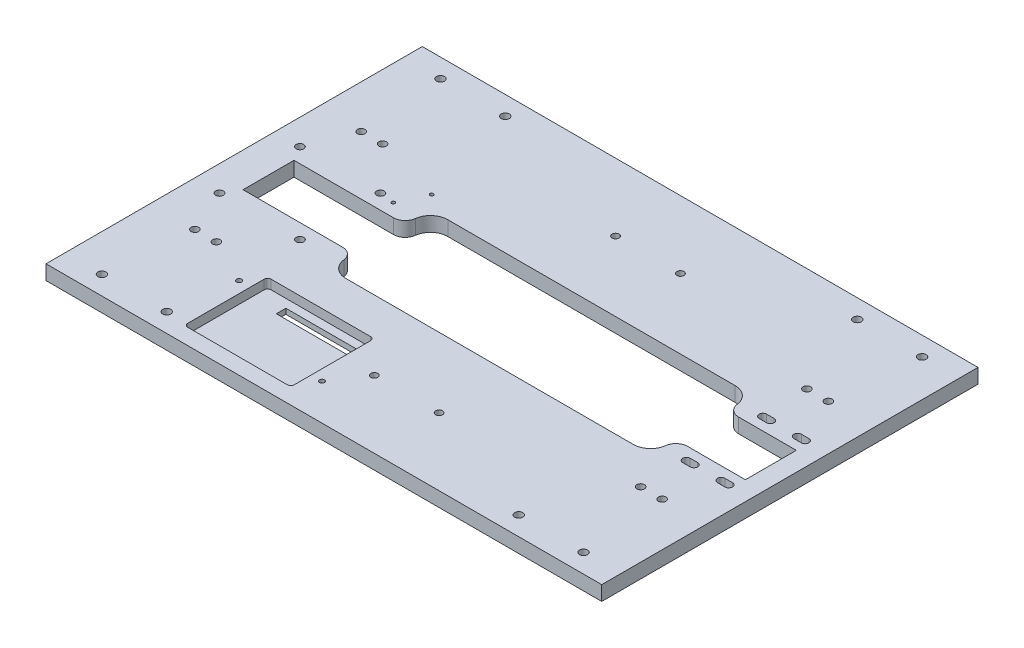
SolidWorks part; units mm, degrees
ref_plane "Front Plane" through (0, 0, 0) normal (0, 0, 1) x (1, 0, 0)
ref_plane "Top Plane" through (0, 0, 0) normal (0, 1, 0) x (1, 0, 0)
ref_plane "Right Plane" through (0, 0, 0) normal (1, 0, 0) x (0, 0, -1)
sketch "Sketch1" plane through (0, 0, 0) normal (0, 1, 0) x (1, 0, 0)
  line L1 (-240, 162.5) -> (240, 162.5)
  line L2 (-240, 162.5) -> (-240, -162.5)
  line L3 (-240, -162.5) -> (240, -162.5)
  line L4 (240, 162.5) -> (240, -162.5)
  line L5 (-240, 162.5) -> (240, -162.5) construction
  line L6 (-240, -162.5) -> (240, 162.5) construction
  point P0 (0, 0)
  dimension "D1" = 480
  dimension "D2" = 325
extrude "Boss-Extrude1" add sketch "Sketch1" along normal blind 12.6
sketch "Sketch2" plane through (0, 0, 0) normal (0, -1, 0) x (1, 0, 0)
  circle A0 centre (41.2474, -104.2) radius 3
  circle A1 centre (-14.7526, -104.2) radius 3
  circle A2 centre (41.2474, 104.2) radius 3
  circle A3 centre (-14.7526, 104.2) radius 3
extrude "Cut-Extrude1" cut sketch "Sketch2" against normal up to next
sketch "Sketch3" plane through (0, 0, 0) normal (0, -1, 0) x (1, 0, 0)
  line L0 (-192.4406, 0) -> (188.5847, 0) construction
  line L1 (163.5847, 44) -> (-114.2887, 44)
  line L2 (163.5847, 44) -> (163.5847, 22)
  line L3 (163.5847, -44) -> (-114.2887, -44)
  line L5 (-114.2887, -44) -> (-114.2887, -22)
  line L6 (-114.2887, -22) -> (-210.2887, -22)
  line L7 (-114.2887, 44) -> (-114.2887, 22)
  line L8 (-114.2887, 22) -> (-210.2887, 22)
  line L9 (-210.2887, 22) -> (-210.2887, -22)
  line L10 (163.5847, 22) -> (223.5847, 22)
  line L11 (223.5847, 22) -> (223.5847, -22)
  line L12 (223.5847, -22) -> (163.5847, -22)
  line L13 (163.5847, -22) -> (163.5847, -44)
  point P0 (0, 0)
  point P1 (-210.2887, 0)
  dimension "D2" = 96
  dimension "D1" = 22
  dimension "D5" = 60
extrude "Cut-Extrude2" cut sketch "Sketch3" against normal up to next
fillet "Fillet1" radius 10 2 edges at (-114.2887, 6.3, 22) (-114.2887, 6.3, -22)
sketch "Sketch4" plane through (0, 0, 0) normal (0, -1, 0) x (1, 0, 0)
  circle A12 centre (-148.4257, -34.75) radius 3.3
  circle A13 centre (-148.4257, 34.75) radius 3.3
  circle A14 centre (-217.9257, 34.75) radius 3.3
  circle A15 centre (-217.9257, -34.75) radius 3.3
extrude "Cut-Extrude3" cut sketch "Sketch4" against normal up to next
fillet "Fillet2" radius 10 2 edges at (163.5847, 6.3, -22) (163.5847, 6.3, 22)
sketch "Sketch7" plane through (0, 12.6, 0) normal (0, 1, 0) x (1, 0, 0)
  circle A0 centre (208, -146.2) radius 2.25
  circle A1 centre (152, -146.2) radius 2.25
  circle A2 centre (-152, -146.2) radius 2.25
  circle A3 centre (-208, -146.2) radius 2.25
  circle A4 centre (-208, 146.2) radius 2.25
  circle A5 centre (-152, 146.2) radius 2.25
  circle A6 centre (208, 146.2) radius 2.25
  circle A7 centre (152, 146.2) radius 2.25
  circle A9 centre (-143.9752, -91.7292) radius 2.2102
  circle A10 centre (-32.9752, -131.1304) radius 2.1044
  dimension "D1" = 4.5
extrude "Cut-Extrude7" cut sketch "Sketch7" against normal up to next
sketch "Sketch8" plane through (0, 12.6, 0) normal (0, 1, 0) x (1, 0, 0)
  circle A0 centre (208, 146.2) radius 3.5
  circle A1 centre (152, 146.2) radius 3.5
  circle A2 centre (-152, 146.2) radius 3.5
  circle A3 centre (-208, 146.2) radius 3.5
  circle A4 centre (208, -146.2) radius 3.5
  circle A5 centre (152, -146.2) radius 3.5
  circle A6 centre (-208, -146.2) radius 3.5
  circle A7 centre (-152, -146.2) radius 3.5
  dimension "D1" = 7
extrude "Cut-Extrude8" cut sketch "Sketch8" against normal blind 6
sketch "Sketch9" plane through (0, 12.6, 0) normal (0, 1, 0) x (1, 0, 0)
  line L1 (-131.2752, -76.7932) -> (-45.2752, -76.7932)
  line L2 (-134.2752, -79.7932) -> (-134.2752, -145.7932)
  line L3 (-131.2752, -148.7932) -> (-45.2752, -148.7932)
  line L4 (-42.2752, -79.7932) -> (-42.2752, -145.7932)
  arc A0 (-134.2752, -145.7932) -> (-131.2752, -148.7932) centre (-131.2752, -145.7932) ccw
  arc A1 (-45.2752, -148.7932) -> (-42.2752, -145.7932) centre (-45.2752, -145.7932) ccw
  arc A2 (-45.2752, -76.7932) -> (-42.2752, -79.7932) centre (-45.2752, -79.7932) cw
  arc A3 (-131.2752, -76.7932) -> (-134.2752, -79.7932) centre (-131.2752, -79.7932) ccw
  dimension "D5" = 3
sketch "Sketch12" plane through (0, 0, 0) normal (0, -1, 0) x (1, 0, 0)
  circle A0 centre (-135.8148, -33.2631) radius 1.5
  circle A1 centre (-125.2148, -55.8631) radius 1.5
extrude "Cut-Extrude11" cut sketch "Sketch12" against normal up to next
fillet "Fillet3" radius 15 4 edges at (163.5847, 6.3, 44) (163.5847, 6.3, -44) (-114.2887, 6.3, 44) (-114.2887, 6.3, -44)
extrude "Cut-Extrude12" cut sketch "Sketch9" against normal blind 8
sketch "Sketch14" plane through (0, 4.6, 0) normal (0, 1, 0) x (1, 0, 0)
  line L1 (-111.1572, -84.1633) -> (-47.573, -84.1633)
  line L2 (-111.1572, -84.1633) -> (-111.1572, -92.4204)
  line L3 (-111.1572, -92.4204) -> (-47.573, -92.4204)
  line L4 (-47.573, -84.1633) -> (-47.573, -92.4204)
extrude "Cut-Extrude13" cut sketch "Sketch14" against normal through all
sketch "Sketch15" plane through (0, 12.6, 0) normal (0, 1, 0) x (1, 0, 0)
  circle A0 centre (-201.3752, -72.5) radius 3.25 construction
  circle A1 centre (-182.8647, -72.5) radius 3.25 construction
  circle A2 centre (-202.7941, 72.5) radius 3.25 construction
  circle A3 centre (-184.2837, 72.5) radius 3.25 construction
  circle A4 centre (182.2059, 72.5) radius 3.25 construction
  circle A5 centre (200.7163, 72.5) radius 3.25 construction
  circle A6 centre (183.6248, -72.5) radius 3.25 construction
  circle A7 centre (202.1353, -72.5) radius 3.25 construction
  circle A8 centre (-201.3752, -72.5) radius 3.25
  circle A9 centre (-182.8647, -72.5) radius 3.25
  circle A10 centre (-202.7941, 72.5) radius 3.25
  circle A11 centre (-184.2837, 72.5) radius 3.25
  circle A12 centre (182.2059, 72.5) radius 3.25
  circle A13 centre (200.7163, 72.5) radius 3.25
  circle A14 centre (183.6248, -72.5) radius 3.25
  circle A15 centre (202.1353, -72.5) radius 3.25
extrude "Cut-Extrude14" cut sketch "Sketch15" against normal up to next
sketch "Sketch16" plane through (0, 12.6, 0) normal (0, 1, 0) x (1, 0, 0)
  line L0 (183.6729, -33) -> (186.9229, -33) construction
  line L1 (213.6729, -33) -> (216.9229, -33) construction
  line L2 (183.6729, 33) -> (186.9229, 33) construction
  line L3 (213.6729, 33) -> (216.9229, 33) construction
  line L4 (183.6729, -36.25) -> (190.1729, -36.25)
  line L5 (183.6729, -29.75) -> (190.1729, -29.75)
  line L6 (213.6729, -36.25) -> (220.1729, -36.25)
  line L7 (213.6729, -29.75) -> (220.1729, -29.75)
  line L8 (183.6729, 29.75) -> (190.1729, 29.75)
  line L9 (183.6729, 36.25) -> (190.1729, 36.25)
  line L10 (213.6729, 29.75) -> (220.1729, 29.75)
  line L11 (213.6729, 36.25) -> (220.1729, 36.25)
  arc A4 (213.6729, -29.75) -> (213.6729, -36.25) centre (213.6729, -33) ccw
  arc A5 (183.6729, -29.75) -> (183.6729, -36.25) centre (183.6729, -33) ccw
  arc A6 (183.6729, 36.25) -> (183.6729, 29.75) centre (183.6729, 33) ccw
  arc A7 (213.6729, 36.25) -> (213.6729, 29.75) centre (213.6729, 33) ccw
  arc A8 (190.1729, -36.25) -> (190.1729, -29.75) centre (190.1729, -33) ccw
  arc A9 (220.1729, -36.25) -> (220.1729, -29.75) centre (220.1729, -33) ccw
  arc A10 (220.1729, 29.75) -> (220.1729, 36.25) centre (220.1729, 33) ccw
  arc A11 (190.1729, 29.75) -> (190.1729, 36.25) centre (190.1729, 33) ccw
  dimension "D1" = 6.5
  dimension "D2" = 6.5
  dimension "D3" = 6.5
  dimension "D4" = 6.5
extrude "Cut-Extrude15" cut sketch "Sketch16" against normal up to next
sketch "Sketch17" plane through (0, 12.6, 0) normal (0, 1, 0) x (1, 0, 0)
  line L4 (240, -162.5) -> (240, 162.5)
  line L5 (240, 162.5) -> (-240, 162.5)
  line L6 (-240, 162.5) -> (-240, -162.5)
  line L7 (-240, -162.5) -> (240, -162.5)
  line L8 (240, -162.5) -> (240, 162.5)
  line L9 (240, 162.5) -> (-240, 162.5)
  line L10 (-240, 162.5) -> (-240, -162.5)
  line L11 (-240, -162.5) -> (240, -162.5)
  line L14 (220.1729, -29.75) -> (213.6729, -29.75)
  line L15 (213.6729, -36.25) -> (220.1729, -36.25)
  line L16 (220.1729, -29.75) -> (213.6729, -29.75)
  line L17 (213.6729, -36.25) -> (220.1729, -36.25)
  line L18 (190.1729, -29.75) -> (183.6729, -29.75)
  line L19 (183.6729, -36.25) -> (190.1729, -36.25)
  line L20 (190.1729, -29.75) -> (183.6729, -29.75)
  line L21 (183.6729, -36.25) -> (190.1729, -36.25)
  line L22 (220.1729, 36.25) -> (213.6729, 36.25)
  line L23 (213.6729, 29.75) -> (220.1729, 29.75)
  line L24 (220.1729, 36.25) -> (213.6729, 36.25)
  line L25 (213.6729, 29.75) -> (220.1729, 29.75)
  line L26 (190.1729, 36.25) -> (183.6729, 36.25)
  line L27 (183.6729, 29.75) -> (190.1729, 29.75)
  line L28 (190.1729, 36.25) -> (183.6729, 36.25)
  line L29 (183.6729, 29.75) -> (190.1729, 29.75)
  line L33 (-134.2752, -79.7932) -> (-134.2752, -145.7932)
  line L34 (-45.2752, -76.7932) -> (-131.2752, -76.7932)
  line L35 (-42.2752, -145.7932) -> (-42.2752, -79.7932)
  line L36 (148.7654, 44) -> (-99.4693, 44)
  line L37 (223.5847, 22) -> (173.5847, 22)
  line L38 (223.5847, -22) -> (223.5847, 22)
  line L39 (173.5847, -22) -> (223.5847, -22)
  line L40 (-99.4693, -44) -> (148.7654, -44)
  line L41 (-210.2887, -22) -> (-124.2887, -22)
  line L42 (-210.2887, 22) -> (-210.2887, -22)
  line L43 (-124.2887, 22) -> (-210.2887, 22)
  line L44 (148.7654, 44) -> (-99.4693, 44)
  line L45 (223.5847, 22) -> (173.5847, 22)
  line L46 (223.5847, -22) -> (223.5847, 22)
  line L47 (173.5847, -22) -> (223.5847, -22)
  line L48 (-99.4693, -44) -> (148.7654, -44)
  line L49 (-210.2887, -22) -> (-124.2887, -22)
  line L50 (-210.2887, 22) -> (-210.2887, -22)
  line L51 (-124.2887, 22) -> (-210.2887, 22)
  line L52 (-131.2752, -148.7932) -> (-45.2752, -148.7932)
  line L53 (-134.2752, -79.7932) -> (-134.2752, -145.7932)
  line L54 (-45.2752, -76.7932) -> (-131.2752, -76.7932)
  line L55 (-42.2752, -145.7932) -> (-42.2752, -79.7932)
  line L56 (-131.2752, -148.7932) -> (-45.2752, -148.7932)
  line L58 (-111.1572, -84.1633) -> (-111.1572, -92.4204)
  line L59 (-47.573, -84.1633) -> (-111.1572, -84.1633)
  line L60 (-47.573, -92.4204) -> (-47.573, -84.1633)
  line L61 (-111.1572, -92.4204) -> (-47.573, -92.4204)
  line L62 (-111.1572, -84.1633) -> (-111.1572, -92.4204)
  line L63 (-47.573, -84.1633) -> (-111.1572, -84.1633)
  line L64 (-47.573, -92.4204) -> (-47.573, -84.1633)
  line L65 (-111.1572, -92.4204) -> (-47.573, -92.4204)
  circle A0 centre (208, 146.2) radius 3.5 construction
  circle A1 centre (208, 146.2) radius 2.25 construction
  circle A2 centre (152, 146.2) radius 3.5 construction
  circle A3 centre (152, 146.2) radius 2.25 construction
  circle A4 centre (-14.7526, 104.2) radius 3 construction
  circle A5 centre (41.2474, 104.2) radius 3 construction
  circle A6 centre (200.7163, 72.5) radius 3.25 construction
  circle A7 centre (182.2059, 72.5) radius 3.25 construction
  circle A8 centre (202.1353, -72.5) radius 3.25 construction
  circle A9 centre (183.6248, -72.5) radius 3.25 construction
  circle A10 centre (208, -146.2) radius 3.5 construction
  circle A11 centre (208, -146.2) radius 2.25 construction
  circle A12 centre (152, -146.2) radius 3.5 construction
  circle A13 centre (152, -146.2) radius 2.25 construction
  circle A14 centre (41.2474, -104.2) radius 3 construction
  circle A15 centre (-14.7526, -104.2) radius 3 construction
  circle A16 centre (-152, -146.2) radius 2.25 construction
  circle A17 centre (-152, -146.2) radius 3.5 construction
  circle A18 centre (-208, -146.2) radius 3.5 construction
  circle A19 centre (-208, -146.2) radius 2.25 construction
  circle A20 centre (-182.8647, -72.5) radius 3.25 construction
  circle A21 centre (-201.3752, -72.5) radius 3.25 construction
  circle A22 centre (-217.9257, -34.75) radius 3.3 construction
  circle A23 centre (-148.4257, -34.75) radius 3.3 construction
  circle A24 centre (-125.2148, 55.8631) radius 1.5 construction
  circle A25 centre (-135.8148, 33.2631) radius 1.5 construction
  circle A26 centre (-148.4257, 34.75) radius 3.3 construction
  circle A27 centre (-217.9257, 34.75) radius 3.3 construction
  circle A28 centre (-184.2837, 72.5) radius 3.25 construction
  circle A29 centre (-202.7941, 72.5) radius 3.25 construction
  circle A30 centre (-152, 146.2) radius 2.25 construction
  circle A31 centre (-152, 146.2) radius 3.5 construction
  circle A32 centre (-208, 146.2) radius 2.25 construction
  circle A33 centre (-208, 146.2) radius 3.5 construction
  circle A34 centre (208, 146.2) radius 3.5
  circle A35 centre (208, 146.2) radius 2.25
  circle A36 centre (152, 146.2) radius 3.5
  circle A37 centre (152, 146.2) radius 2.25
  circle A38 centre (-14.7526, 104.2) radius 3
  circle A39 centre (41.2474, 104.2) radius 3
  circle A40 centre (200.7163, 72.5) radius 3.25
  circle A41 centre (182.2059, 72.5) radius 3.25
  circle A42 centre (202.1353, -72.5) radius 3.25
  circle A43 centre (183.6248, -72.5) radius 3.25
  circle A44 centre (208, -146.2) radius 3.5
  circle A45 centre (208, -146.2) radius 2.25
  circle A46 centre (152, -146.2) radius 3.5
  circle A47 centre (152, -146.2) radius 2.25
  circle A48 centre (41.2474, -104.2) radius 3
  circle A49 centre (-14.7526, -104.2) radius 3
  circle A50 centre (-152, -146.2) radius 2.25
  circle A51 centre (-152, -146.2) radius 3.5
  circle A52 centre (-208, -146.2) radius 3.5
  circle A53 centre (-208, -146.2) radius 2.25
  circle A54 centre (-182.8647, -72.5) radius 3.25
  circle A55 centre (-201.3752, -72.5) radius 3.25
  circle A56 centre (-217.9257, -34.75) radius 3.3
  circle A57 centre (-148.4257, -34.75) radius 3.3
  circle A58 centre (-125.2148, 55.8631) radius 1.5
  circle A59 centre (-135.8148, 33.2631) radius 1.5
  circle A60 centre (-148.4257, 34.75) radius 3.3
  circle A61 centre (-217.9257, 34.75) radius 3.3
  circle A62 centre (-184.2837, 72.5) radius 3.25
  circle A63 centre (-202.7941, 72.5) radius 3.25
  circle A64 centre (-152, 146.2) radius 2.25
  circle A65 centre (-152, 146.2) radius 3.5
  circle A66 centre (-208, 146.2) radius 2.25
  circle A67 centre (-208, 146.2) radius 3.5
  circle A68 centre (-32.9752, -131.1304) radius 2.1044 construction
  circle A69 centre (-143.9752, -91.7292) radius 2.2102 construction
  arc A70 (213.6729, -29.75) -> (213.6729, -36.25) centre (213.6729, -33) ccw
  arc A71 (220.1729, -36.25) -> (220.1729, -29.75) centre (220.1729, -33) ccw
  arc A72 (213.6729, -29.75) -> (213.6729, -36.25) centre (213.6729, -33) ccw
  arc A73 (220.1729, -36.25) -> (220.1729, -29.75) centre (220.1729, -33) ccw
  arc A74 (183.6729, -29.75) -> (183.6729, -36.25) centre (183.6729, -33) ccw
  arc A75 (190.1729, -36.25) -> (190.1729, -29.75) centre (190.1729, -33) ccw
  arc A76 (183.6729, -29.75) -> (183.6729, -36.25) centre (183.6729, -33) ccw
  arc A77 (190.1729, -36.25) -> (190.1729, -29.75) centre (190.1729, -33) ccw
  arc A78 (213.6729, 36.25) -> (213.6729, 29.75) centre (213.6729, 33) ccw
  arc A79 (220.1729, 29.75) -> (220.1729, 36.25) centre (220.1729, 33) ccw
  arc A80 (213.6729, 36.25) -> (213.6729, 29.75) centre (213.6729, 33) ccw
  arc A81 (220.1729, 29.75) -> (220.1729, 36.25) centre (220.1729, 33) ccw
  arc A82 (183.6729, 36.25) -> (183.6729, 29.75) centre (183.6729, 33) ccw
  arc A83 (190.1729, 29.75) -> (190.1729, 36.25) centre (190.1729, 33) ccw
  arc A84 (183.6729, 36.25) -> (183.6729, 29.75) centre (183.6729, 33) ccw
  arc A85 (190.1729, 29.75) -> (190.1729, 36.25) centre (190.1729, 33) ccw
  circle A86 centre (-32.9752, -131.1304) radius 2.1044
  circle A87 centre (-143.9752, -91.7292) radius 2.2102
  arc A88 (-134.2752, -145.7932) -> (-131.2752, -148.7932) centre (-131.2752, -145.7932) ccw
  arc A89 (-131.2752, -76.7932) -> (-134.2752, -79.7932) centre (-131.2752, -79.7932) ccw
  arc A90 (-42.2752, -79.7932) -> (-45.2752, -76.7932) centre (-45.2752, -79.7932) ccw
  arc A91 (-45.2752, -148.7932) -> (-42.2752, -145.7932) centre (-45.2752, -145.7932) ccw
  arc A92 (163.657, 30.8) -> (148.7654, 44) centre (148.7654, 29) ccw
  arc A93 (163.657, 30.8) -> (173.5847, 22) centre (173.5847, 32) ccw
  arc A94 (173.5847, -22) -> (163.657, -30.8) centre (173.5847, -32) ccw
  arc A95 (148.7654, -44) -> (163.657, -30.8) centre (148.7654, -29) ccw
  arc A96 (-114.3609, -30.8) -> (-99.4693, -44) centre (-99.4693, -29) ccw
  arc A97 (-114.3609, -30.8) -> (-124.2887, -22) centre (-124.2887, -32) ccw
  arc A98 (-124.2887, 22) -> (-114.3609, 30.8) centre (-124.2887, 32) ccw
  arc A99 (-99.4693, 44) -> (-114.3609, 30.8) centre (-99.4693, 29) ccw
  arc A100 (163.657, 30.8) -> (148.7654, 44) centre (148.7654, 29) ccw
  arc A101 (163.657, 30.8) -> (173.5847, 22) centre (173.5847, 32) ccw
  arc A102 (173.5847, -22) -> (163.657, -30.8) centre (173.5847, -32) ccw
  arc A103 (148.7654, -44) -> (163.657, -30.8) centre (148.7654, -29) ccw
  arc A104 (-114.3609, -30.8) -> (-99.4693, -44) centre (-99.4693, -29) ccw
  arc A105 (-114.3609, -30.8) -> (-124.2887, -22) centre (-124.2887, -32) ccw
  arc A106 (-124.2887, 22) -> (-114.3609, 30.8) centre (-124.2887, 32) ccw
  arc A107 (-99.4693, 44) -> (-114.3609, 30.8) centre (-99.4693, 29) ccw
  arc A108 (-134.2752, -145.7932) -> (-131.2752, -148.7932) centre (-131.2752, -145.7932) ccw
  arc A109 (-131.2752, -76.7932) -> (-134.2752, -79.7932) centre (-131.2752, -79.7932) ccw
  arc A110 (-42.2752, -79.7932) -> (-45.2752, -76.7932) centre (-45.2752, -79.7932) ccw
  arc A111 (-45.2752, -148.7932) -> (-42.2752, -145.7932) centre (-45.2752, -145.7932) ccw
  dimension "D1" = 0
  dimension "D2" = 0
  dimension "D3" = 0
  dimension "D4" = 0
  dimension "D5" = 0
  dimension "D6" = 0
  dimension "D7" = 0
  dimension "D8" = 0
